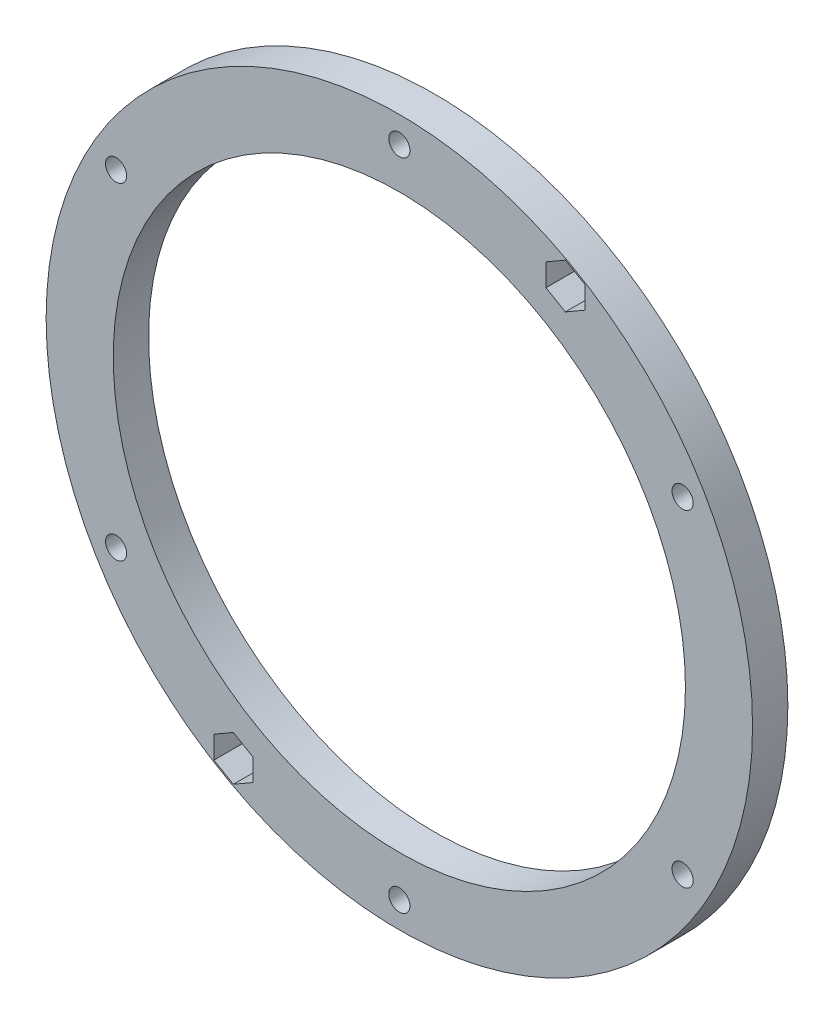
SolidWorks part; units mm, degrees
ref_plane "Plan de face" through (0, 0, 0) normal (0, 0, 1) x (1, 0, 0)
ref_plane "Plan de dessus" through (0, 0, 0) normal (0, 1, 0) x (1, 0, 0)
ref_plane "Plan de droite" through (0, 0, 0) normal (1, 0, 0) x (0, 0, -1)
sketch "Esquisse1" plane through (0, 0, 0) normal (0, 0, 1) x (1, 0, 0)
  line L0 (53.6751, 0) -> (-86.559, 0) construction
  line L1 (0, 50) -> (0, -56.2363) construction
  line L2 (0, 0) -> (70.5826, 40.7509) construction
  line L3 (0, 0) -> (-77.9761, 45.0195) construction
  line L4 (5, 46.3) -> (-5, 46.3) construction
  line L5 (42.597, 18.8199) -> (37.597, 27.4801) construction
  line L6 (37.597, -27.4801) -> (42.597, -18.8199) construction
  line L7 (-5, -46.3) -> (5, -46.3) construction
  line L8 (-42.597, -18.8199) -> (-37.597, -27.4801) construction
  line L9 (-37.597, 27.4801) -> (-42.597, 18.8199) construction
  line L10 (-33.3333, 0) -> (0, 0) construction
  line L14 (0, 46.3) -> (0, 39.3276) construction
  line L16 (40.097, 23.15) -> (34.0587, 19.6638) construction
  line L18 (40.097, -23.15) -> (34.0587, -19.6638) construction
  line L20 (0, -46.3) -> (0, -39.3276) construction
  line L22 (-40.097, -23.15) -> (-34.0587, -19.6638) construction
  line L24 (-40.097, 23.15) -> (-34.0587, 19.6638) construction
  circle A0 centre (0, 0) radius 50
  circle A1 centre (33.3333, 0) radius 16.6667 construction
  circle A2 centre (16.6667, -28.8675) radius 16.6667 construction
  circle A3 centre (-16.6667, -28.8675) radius 16.6667 construction
  circle A4 centre (-33.3333, 0) radius 16.6667 construction
  circle A5 centre (-16.6667, 28.8675) radius 16.6667 construction
  circle A6 centre (16.6667, 28.8675) radius 16.6667 construction
  circle A7 centre (0, 46.3) radius 1.5
  circle A8 centre (40.097, 23.15) radius 1.5
  circle A9 centre (40.097, -23.15) radius 1.5
  circle A10 centre (0, -46.3) radius 1.5
  circle A11 centre (-40.097, -23.15) radius 1.5
  circle A12 centre (-40.097, 23.15) radius 1.5
  circle A14 centre (0, 0) radius 16.6667 construction
  point P20 (0, 0)
  point P30 (0, 0)
  point P48 (-16.6667, 0)
  point P54 (0, 0)
  point P60 (0, 0)
  point P117 (0, 0)
  dimension "D1" = 6
  dimension "D2" = 30
  dimension "D5" = 3
  dimension "D6" = 46.3
  dimension "D8" = 3
  dimension "D10" = 3
  dimension "D9" = 3
  dimension "D7" = 3
  dimension "D11" = 3
  dimension "D3" = 30
sketch_block_instance "Trou M3 plots 5mm-8"
sketch_block "Trou M3 plots 5mm" parameters "D2"=3, "D1"=5, "D3"=5, "D4"=10
sketch_block_instance "Trou M3 plots 5mm-9"
extrude "Boss.-Extru.1" add sketch "Esquisse1" along normal blind 5
sketch "Sketch3" plane through (0, 0, 5) normal (0, 0, 1) x (1, 0, 0)
  line L0 (53.6751, 0) -> (-86.559, 0) construction
  line L6 (16.6667, 28.8675) -> (-16.6667, -28.8675) construction
  line L7 (-23.3333, 4) -> (-22.3333, 4)
  line L8 (-23.3333, 4) -> (-23.3333, -4)
  line L9 (-23.3333, -4) -> (-22.3333, -4)
  line L10 (-22.3333, 4) -> (-22.3333, -4)
  line L11 (-16.6667, 28.8675) -> (16.6667, -28.8675) construction
  line L12 (-13.2337, 23.9214) -> (-14.0997, 23.4214)
  line L13 (-14.0997, 23.4214) -> (-12.3497, 20.3903)
  line L14 (-12.3497, 20.3903) -> (-15.3808, 18.6403)
  line L15 (-15.3808, 18.6403) -> (-14.8808, 17.7742)
  line L16 (-14.8808, 17.7742) -> (-11.8497, 19.5242)
  line L17 (-11.8497, 19.5242) -> (-10.0997, 16.4932)
  line L18 (-10.0997, 16.4932) -> (-9.2337, 16.9932)
  line L19 (-9.2337, 16.9932) -> (-10.9837, 20.0242)
  line L20 (-10.9837, 20.0242) -> (-7.9526, 21.7742)
  line L21 (-7.9526, 21.7742) -> (-8.4526, 22.6403)
  line L22 (-8.4526, 22.6403) -> (-11.4837, 20.8903)
  line L23 (-11.4837, 20.8903) -> (-13.2337, 23.9214)
  line L24 (-16.2531, 17.5593) -> (-5.3419, 23.8588) construction
  line L25 (-14.6252, 25.3316) -> (-8.4936, 14.7114) construction
  line L26 (15.1308, 18.2073) -> (14.6308, 17.3412)
  line L27 (15.1308, 18.2073) -> (8.2026, 22.2073)
  line L28 (8.2026, 22.2073) -> (7.7026, 21.3412)
  line L29 (14.6308, 17.3412) -> (7.7026, 21.3412)
  line L30 (8.2026, -22.2073) -> (7.7026, -21.3412)
  line L31 (8.2026, -22.2073) -> (15.1308, -18.2073)
  line L32 (15.1308, -18.2073) -> (14.6308, -17.3412)
  line L33 (7.7026, -21.3412) -> (14.6308, -17.3412)
  line L34 (27.3333, -0.5) -> (27.3333, 0.5)
  line L35 (27.3333, 0.5) -> (23.8333, 0.5)
  line L36 (23.8333, 0.5) -> (23.8333, 4)
  line L37 (23.8333, 4) -> (22.8333, 4)
  line L38 (22.8333, 4) -> (22.8333, 0.5)
  line L39 (22.8333, 0.5) -> (19.3333, 0.5)
  line L40 (19.3333, 0.5) -> (19.3333, -0.5)
  line L41 (19.3333, -0.5) -> (22.8333, -0.5)
  line L42 (22.8333, -0.5) -> (22.8333, -4)
  line L43 (22.8333, -4) -> (23.8333, -4)
  line L44 (23.8333, -4) -> (23.8333, -0.5)
  line L45 (23.8333, -0.5) -> (27.3333, -0.5)
  line L46 (-14.0997, -23.4214) -> (-13.2337, -23.9214)
  line L47 (-13.2337, -23.9214) -> (-11.4837, -20.8903)
  line L48 (-11.4837, -20.8903) -> (-8.4526, -22.6403)
  line L49 (-8.4526, -22.6403) -> (-7.9526, -21.7742)
  line L50 (-7.9526, -21.7742) -> (-10.9837, -20.0242)
  line L51 (-10.9837, -20.0242) -> (-9.2337, -16.9932)
  line L52 (-9.2337, -16.9932) -> (-10.0997, -16.4932)
  line L53 (-10.0997, -16.4932) -> (-11.8497, -19.5242)
  line L54 (-11.8497, -19.5242) -> (-14.8808, -17.7742)
  line L55 (-14.8808, -17.7742) -> (-15.3808, -18.6403)
  line L56 (-15.3808, -18.6403) -> (-12.3497, -20.3903)
  line L57 (-12.3497, -20.3903) -> (-14.0997, -23.4214)
  line L58 (-21.8333, 14.2784) -> (-24.4284, 9.7836) construction
  line L59 (173205.0808, -100000) -> (-173283.0568, 100045.0195) construction
  line L60 (-7.433, 11.8744) -> (-5.683, 8.8433)
  line L61 (-6.567, 12.3744) -> (-7.433, 11.8744)
  line L62 (-7.8805, 13.6494) -> (-1.7489, 3.0291) construction
  line L63 (-2.567, 5.4462) -> (-4.317, 8.4772)
  line L64 (-1.2859, 10.2272) -> (-1.7859, 11.0933)
  line L65 (-3.433, 4.9462) -> (-2.567, 5.4462)
  line L66 (-4.317, 8.4772) -> (-1.2859, 10.2272)
  line L67 (-8.7141, 7.0933) -> (-8.2141, 6.2272)
  line L68 (-8.2141, 6.2272) -> (-5.183, 7.9772)
  line L69 (-4.817, 9.3433) -> (-6.567, 12.3744)
  line L70 (-1.7859, 11.0933) -> (-4.817, 9.3433)
  line L71 (-5.183, 7.9772) -> (-3.433, 4.9462)
  line L72 (-5.683, 8.8433) -> (-8.7141, 7.0933)
  line L73 (-9.0607, 6.3158) -> (-0.8395, 11.0623) construction
  line L74 (-173205.0808, -100000) -> (173275.6634, 100040.7509) construction
  text T0 "+"
  point P2 (-8.4641, 6.6603)
  point P4 (-1.5359, 10.6603)
  point P36 (-8.2026, 22.2073)
  point P39 (-13.6667, 23.6714)
  point P51 (0, 0)
  point P75 (0, 0)
  point P85 (-23.3333, 0)
  point P92 (-1.5413, 10.6572)
  dimension "D2" = 1
  dimension "D3" = 10
  dimension "D4" = 1
  dimension "D5" = 8
  dimension "D6" = 10
  dimension "D7" = 1
  dimension "D8" = 1
  dimension "D9" = 8
  dimension "D10" = 8
  dimension "D11" = 4
  dimension "D12" = 4
  dimension "D13" = 10
  dimension "D16" = 1
  dimension "D14" = 3
  dimension "D15" = 3
sketch "Sketch4" plane through (0, 0, 5) normal (0, 0, 1) x (1, 0, 0)
  line L0 (-0.3929, -0.6806) -> (-32.7522, -56.7285) construction
  line L1 (0, 0) -> (0, -46.3) construction
  line L9 (-20.75, -39.1155) -> (-23.5, -37.5278)
  line L10 (-23.5, -37.5278) -> (-26.25, -39.1155)
  line L11 (-26.25, -39.1155) -> (-26.25, -42.2909)
  line L12 (-26.25, -42.2909) -> (-23.5, -43.8786)
  line L13 (-23.5, -43.8786) -> (-20.75, -42.2909)
  line L14 (-20.75, -42.2909) -> (-20.75, -39.1155)
  line L15 (26.25, 42.2909) -> (23.5, 43.8786)
  line L16 (23.5, 43.8786) -> (20.75, 42.2909)
  line L17 (20.75, 42.2909) -> (20.75, 39.1155)
  line L18 (20.75, 39.1155) -> (23.5, 37.5278)
  line L19 (23.5, 37.5278) -> (26.25, 39.1155)
  line L20 (26.25, 39.1155) -> (26.25, 42.2909)
  circle A4 centre (-23.5, -40.7032) radius 2.75 construction
  circle A5 centre (23.5, 40.7032) radius 2.75 construction
  point P18 (0, 0)
  dimension "D2" = 47
  dimension "D1" = 30
extrude "Cut-Extrude4" cut sketch "Sketch4" against normal blind 10
sketch "Sketch5" plane through (0, 0, 5) normal (0, 0, 1) x (1, 0, 0)
  circle A0 centre (0, 0) radius 40.5
extrude "Cut-Extrude5" cut sketch "Sketch5" against normal blind 10
